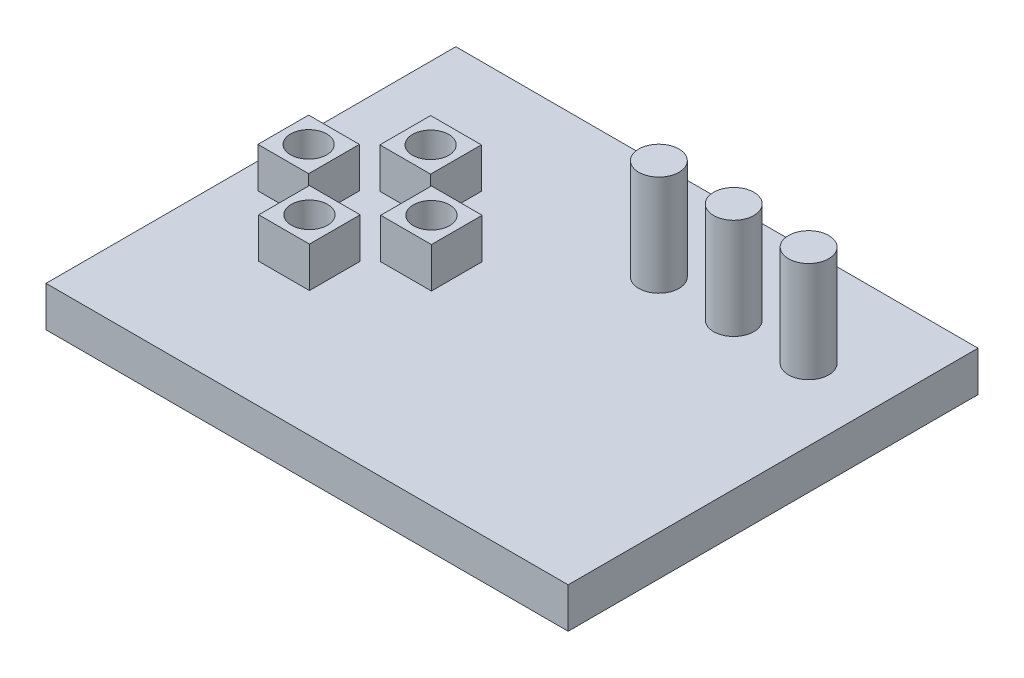
SolidWorks part; units mm, degrees
ref_plane "Front Plane" through (0, 0, 0) normal (0, 0, 1) x (1, 0, 0)
ref_plane "Top Plane" through (0, 0, 0) normal (0, 1, 0) x (1, 0, 0)
ref_plane "Right Plane" through (0, 0, 0) normal (1, 0, 0) x (0, 0, -1)
sketch "Sketch1" plane through (0, 0, 0) normal (0, 1, 0) x (1, 0, 0)
  line L1 (32.425, -25.45) -> (-32.425, -25.45)
  line L2 (32.425, -25.45) -> (32.425, 25.45)
  line L3 (32.425, 25.45) -> (-32.425, 25.45)
  line L4 (-32.425, -25.45) -> (-32.425, 25.45)
  line L5 (32.425, -25.45) -> (-32.425, 25.45) construction
  line L6 (32.425, 25.45) -> (-32.425, -25.45) construction
  point P0 (0, 0)
extrude "Boss-Extrude1" add sketch "Sketch1" along normal blind 5
sketch "Sketch2" plane through (0, 5, 0) normal (0, 1, 0) x (1, 0, 0)
  line L0 (-22.9118, 0.8052) -> (-13.9618, 0.8052) construction
  line L1 (-29.2118, 3.9552) -> (-22.9118, 3.9552)
  line L2 (-29.2118, 3.9552) -> (-29.2118, -2.3448)
  line L3 (-29.2118, -2.3448) -> (-22.9118, -2.3448)
  line L4 (-22.9118, 3.9552) -> (-22.9118, -2.3448)
  line L5 (-29.2118, 3.9552) -> (-22.9118, -2.3448) construction
  line L6 (-29.2118, -2.3448) -> (-22.9118, 3.9552) construction
  line L11 (-7.6618, -2.3448) -> (-13.9618, -2.3448)
  line L12 (-13.9618, 3.9552) -> (-13.9618, -2.3448)
  line L13 (-21.5868, 11.4802) -> (-15.2868, 11.4802)
  line L14 (-7.6618, 3.9552) -> (-13.9618, 3.9552)
  line L15 (-7.6618, 3.9552) -> (-7.6618, -2.3448)
  line L16 (-15.2868, 5.1802) -> (-15.2868, 11.4802)
  line L21 (-18.4368, 5.1802) -> (-18.4368, -3.5698) construction
  line L22 (-21.5868, 5.1802) -> (-15.2868, 5.1802)
  line L23 (-21.5868, 5.1802) -> (-21.5868, 11.4802)
  line L24 (-21.5868, -3.5698) -> (-15.2868, -3.5698)
  line L25 (-21.5868, -3.5698) -> (-21.5868, -9.8698)
  line L26 (-21.5868, -9.8698) -> (-15.2868, -9.8698)
  line L27 (-15.2868, -3.5698) -> (-15.2868, -9.8698)
  line L28 (-18.4368, -3.5698) -> (-18.4368, -9.8698) construction
  line L29 (-32.425, 0.8052) -> (12.1436, 0.8052) construction
  line L30 (-32.425, 25.45) -> (-32.425, -25.45) construction
  circle A0 centre (-26.0618, 0.8052) radius 2.25
  circle A1 centre (-10.8118, 0.8052) radius 2.25
  circle A2 centre (-18.4368, -6.7198) radius 2.25
  circle A3 centre (-18.4368, 8.3302) radius 2.25
  point P0 (-26.0618, 0.8052)
extrude "Boss-Extrude2" add sketch "Sketch2" along normal blind 5
sketch "Sketch3" plane through (0, 5, 0) normal (0, 1, 0) x (1, 0, 0)
  circle A6 centre (4.9342, 13.3052) radius 2.5
  circle A7 centre (14.2342, 13.3052) radius 2.5
  circle A8 centre (23.5342, 13.3052) radius 2.5
  point P7 (0, 0)
extrude "Boss-Extrude3" add sketch "Sketch3" along normal blind 12.5
